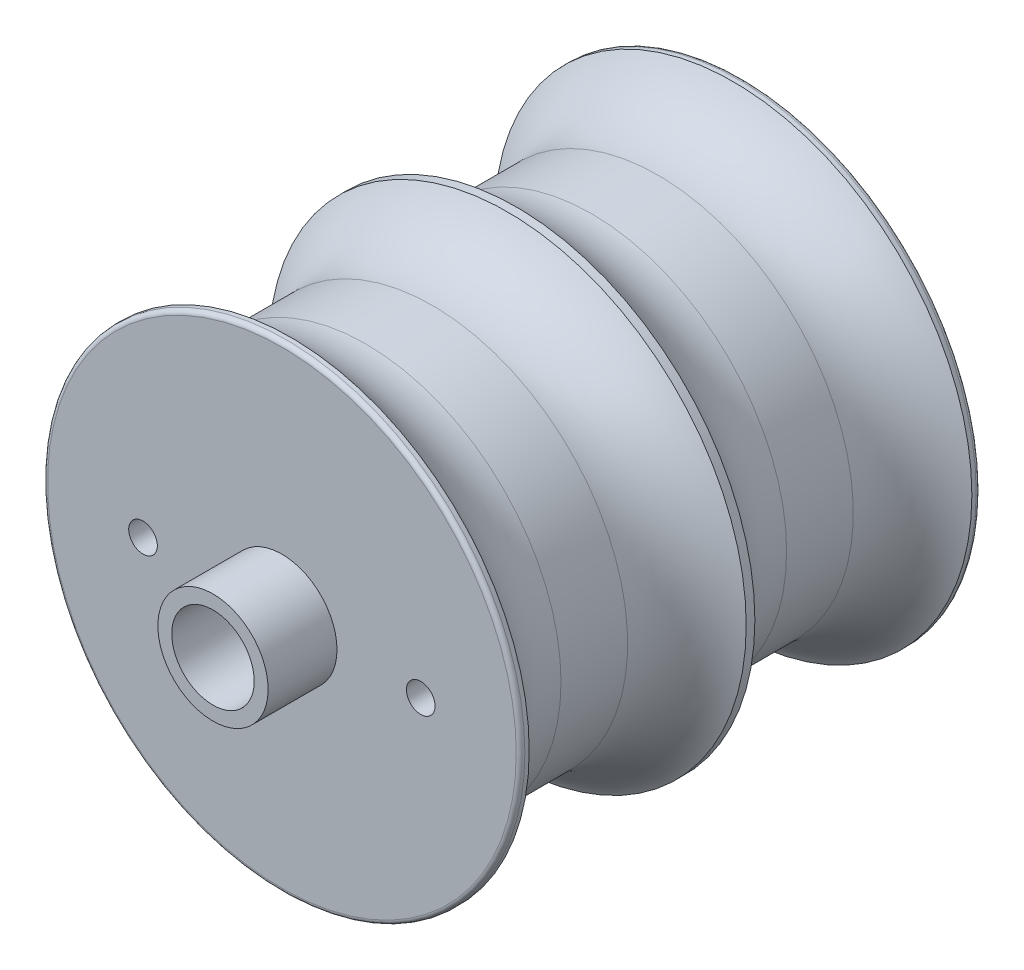
SolidWorks part; units mm, degrees
ref_plane "Front Plane" through (0, 0, 0) normal (0, 0, 1) x (1, 0, 0)
ref_plane "Top Plane" through (0, 0, 0) normal (0, 1, 0) x (1, 0, 0)
ref_plane "Right Plane" through (0, 0, 0) normal (1, 0, 0) x (0, 0, -1)
sketch "Sketch1" plane through (0, 0, 0) normal (0, 0, 1) x (1, 0, 0)
  circle A0 centre (0, 0) radius 22.5
  circle A1 centre (0, 0) radius 27.5
  circle A2 centre (0, 0) radius 4.75
  circle A3 centre (-16, 0) radius 1.65
  circle A4 centre (16, 0) radius 1.65
  circle A5 centre (0, 0) radius 6.35
  dimension "D1" = 45
  dimension "D2" = 55
  dimension "D3" = 9.5
  dimension "D4" = 3.3
  dimension "D7" = 12.7
  dimension "D5" = 16
  dimension "D6" = 16
extrude "Boss-Extrude1" add sketch "Sketch1" along normal blind 1 contours A0 A4 A3 A2 | A1 A0 | A5 A2 region at (-21.8636, 0, 0) region at (-26.7222, 0, 0) region at (-6.1704, 0, 0)
extrude "Boss-Extrude2" add sketch "Sketch1<3>" along normal blind 25 from surface contours A0 A4 A3 A2 | A5 A2 region at (-21.8636, 0, 0) region at (-6.1704, 0, 0) starting at face at (17.65, 0, 1)
sketch "Sketch1<3>" plane through (0, 0, 0) normal (0, 0, 1) x (1, 0, 0) same geometry as "Sketch1"
extrude "Boss-Extrude3" add sketch "Sketch1<4>" along normal blind 1 from surface contours A1 A0 | A0 A4 A3 A2 | A5 A2 region at (-21.8636, 0, 0) region at (-26.7222, 0, 0) region at (-6.1704, 0, 0) starting at face at (-14.35, 0, 26)
sketch "Sketch1<4>" plane through (0, 0, 0) normal (0, 0, 1) x (1, 0, 0) same geometry as "Sketch1"
extrude "Boss-Extrude4" add sketch "Sketch1<5>" along normal blind 25 from surface contours A0 A4 A3 A2 | A5 A2 region at (-21.8636, 0, 0) region at (-6.1704, 0, 0) starting at face at (-14.35, 0, 27)
sketch "Sketch1<5>" plane through (0, 0, 0) normal (0, 0, 1) x (1, 0, 0) same geometry as "Sketch1"
extrude "Boss-Extrude5" add sketch "Sketch1<6>" along normal blind 1 from surface contours A0 A4 A3 A2 | A1 A0 | A5 A2 region at (-21.8636, 0, 0) region at (-26.7222, 0, 0) region at (-6.1704, 0, 0) starting at face at (-14.35, 0, 52)
sketch "Sketch1<6>" plane through (0, 0, 0) normal (0, 0, 1) x (1, 0, 0) same geometry as "Sketch1"
fillet "Fillet1" radius 10 4 edges at (22.5, 0, 26) (22.5, 0, 1) (22.5, 0, 27) (22.5, 0, 52)
fillet "Fillet2" radius 0.5 2 edges at (27.5, 0, 0) (27.5, 0, 53)
extrude "Boss-Extrude6" add sketch "Sketch1<7>" along normal blind 7.938 from surface separate body contours A5 A2 region at (-6.1704, 0, 0) starting at face at (27, 0, 53)
sketch "Sketch1<7>" plane through (0, 0, 0) normal (0, 0, 1) x (1, 0, 0) same geometry as "Sketch1"
